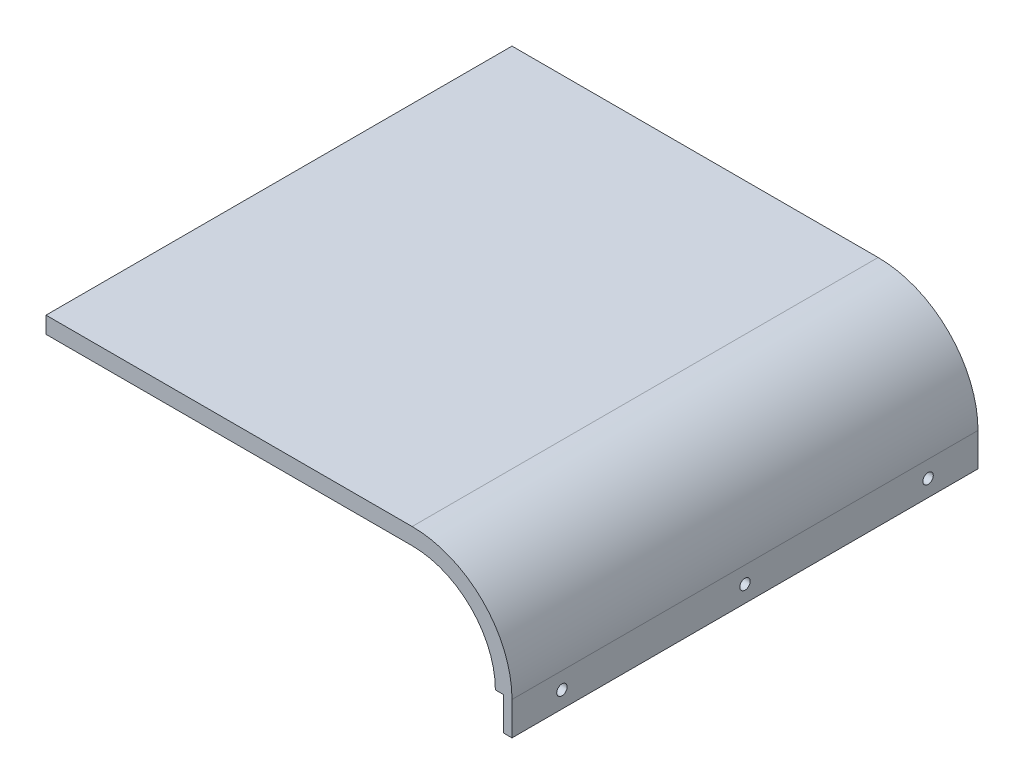
SolidWorks part; units mm, degrees
ref_plane "Front Plane" through (0, 0, 0) normal (0, 0, 1) x (1, 0, 0)
ref_plane "Top Plane" through (0, 0, 0) normal (0, 1, 0) x (1, 0, 0)
ref_plane "Right Plane" through (0, 0, 0) normal (1, 0, 0) x (0, 0, -1)
sketch "Sketch1" plane through (0, 0, 0) normal (0, 0, 1) x (1, 0, 0)
  line L0 (-139.7, 0) -> (139.7, 0)
  line L1 (139.7, 0) -> (139.7, -152.4) construction
  line L2 (139.7, -76.2) -> (215.9, -76.2) construction
  line L3 (-139.7, -12.7) -> (139.7, -12.7)
  line L4 (-139.7, 0) -> (-139.7, -12.7)
  line L5 (215.9, -76.2) -> (203.2, -76.2)
  circle A0 centre (139.7, -76.2) radius 76.2 construction
  arc A1 (139.7, 0) -> (215.9, -76.2) centre (139.7, -76.2) cw
  arc A2 (139.7, -12.7) -> (203.2, -76.2) centre (139.7, -76.2) cw
  point P4 (0, 0)
  dimension "D1" = 152.4
  dimension "D2" = 355.6
  dimension "D3" = 12.7
extrude "Boss-Extrude1" add sketch "Sketch1" along normal blind 177.8 and the other way blind 177.8
sketch "Sketch2" plane through (0, -76.2, 0) normal (0, -1, 0) x (1, 0, 0)
  line L0 (203.2, 177.8) -> (215.9, 177.8) construction
  line L1 (209.55, 177.8) -> (215.9, 177.8)
  line L2 (209.55, 177.8) -> (209.55, -177.8)
  line L3 (209.55, -177.8) -> (215.9, -177.8)
  line L4 (215.9, 177.8) -> (215.9, -177.8)
extrude "Boss-Extrude2" add sketch "Sketch2" along normal blind 25.4
sketch "Sketch3" plane through (215.9, 0, 0) normal (1, 0, 0) x (0, 0, -1)
  line L0 (-177.8, -88.9) -> (177.8, -88.9) construction
  line L1 (-177.8, -101.6) -> (-177.8, -76.2) construction
  line L2 (177.8, -101.6) -> (177.8, -76.2) construction
  line L3 (0, -76.2) -> (0, -101.6) construction
  line L4 (177.8, -76.2) -> (-177.8, -76.2) construction
  line L5 (177.8, -101.6) -> (-177.8, -101.6) construction
  line L6 (139.7, -76.2) -> (139.7, -101.6) construction
  line L7 (-139.7, -76.2) -> (-139.7, -101.6) construction
  circle A0 centre (-139.7, -88.9) radius 3.9687
  circle A1 centre (0, -88.9) radius 3.9687
  circle A2 centre (139.7, -88.9) radius 3.9687
  dimension "D3" = 7.9375
  dimension "D1" = 139.7
  dimension "D2" = 139.7
extrude "Cut-Extrude1" cut sketch "Sketch3" against normal blind 25.4
sketch "Sketch4" plane through (0, 0, 0) normal (0, 1, 0) x (1, 0, 0)
  circle A0 centre (0, 0) radius 63.5
  dimension "D1" = 127
